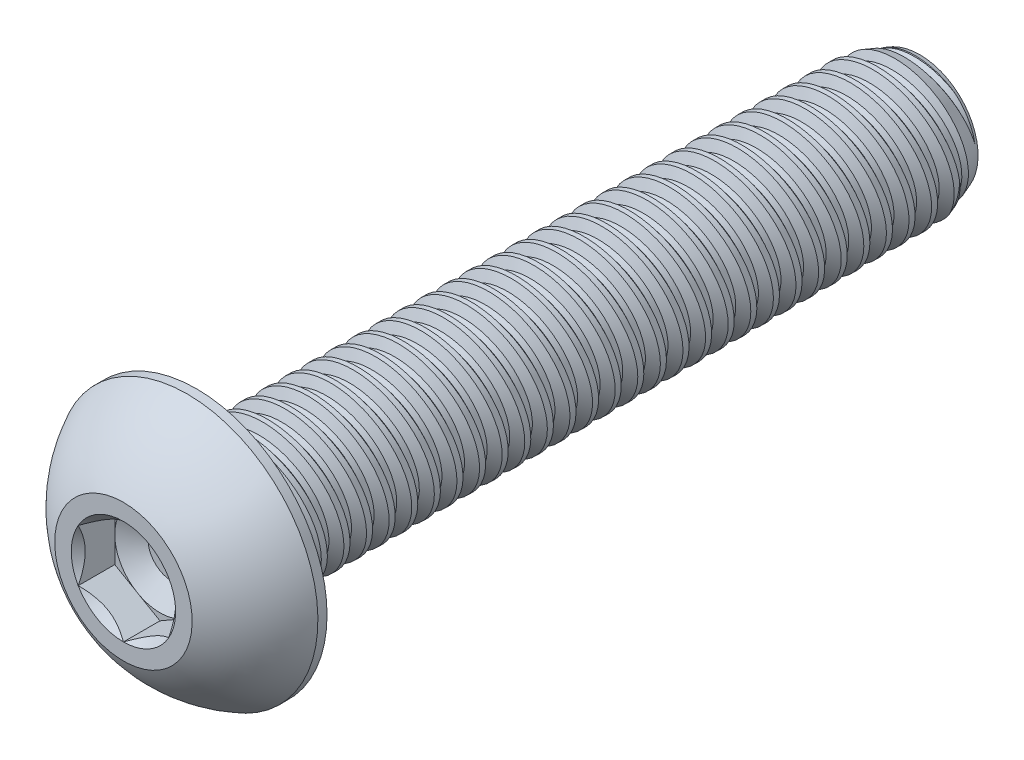
SolidWorks part; units mm, degrees
ref_plane "Front" through (0, 0, 0) normal (0, 0, 1) x (1, 0, 0)
ref_plane "Top" through (0, 0, 0) normal (0, 1, 0) x (1, 0, 0)
ref_plane "Right" through (0, 0, 0) normal (1, 0, 0) x (0, 0, -1)
sketch "Sketch1" plane through (0, 0, 0) normal (1, 0, 0) x (0, 0, -1)
  line L0 (0, 0) -> (-2.5654, 0) construction
  line L1 (0, 0) -> (25.4, 0)
  line L2 (0, 0) -> (0, 2.413)
  line L3 (0, 2.413) -> (25.4, 2.413)
  line L4 (25.4, 0) -> (25.4, 2.413)
  line L5 (0, -2.413) -> (25.4, -2.413) construction
  dimension "D1" = 25.4
  dimension "Thread Dia" = 4.826
  dimension "Length" = 25.4
  dimension "Head Height" = 2.5654
revolve "Revolve1" add sketch "Sketch1" angle 360 about L0
ref_plane "Plane1" through (0, 0, 2.5654) normal (0, 0, 1) x (1, 0, 0)
sketch "Sketch2" plane through (0, 0, 0) normal (1, 0, 0) x (0, 0, -1)
  line L0 (0, 2.413) -> (0, -2.413) construction
  line L1 (0, -2.413) -> (0.7938, -2.413) construction
  line L2 (0.7938, -2.413) -> (0, 2.413) construction
  line L3 (0, 2.413) -> (0.0979, 2.4291) construction
  line L4 (0.0979, 2.4291) -> (0.7832, 2.5418)
  line L5 (0.7832, 2.5418) -> (0.6082, 2.0776)
  line L6 (0.6082, 2.0776) -> (0.4124, 2.0454)
  line L7 (0.4124, 2.0454) -> (0.0979, 2.4291)
  line L8 (0.5103, 2.0615) -> (0.4406, 2.4855) construction
  line L9 (0, -2.413) -> (25.4, -2.413) construction
  line L10 (0, 2.413) -> (25.4, 2.413) construction
  line L12 (0.4525, 2.413) -> (1.2462, -2.413) construction
  line L13 (0, -0.1397) -> (1.6987, 0.1397) construction
  line L15 (0, 0) -> (0, 2.413) construction
  point P19 (0.8494, 0)
  dimension "D1" = 60
  dimension "Thread Pitch" = 0.7937
  dimension "D2" = 0.0992
  dimension "D3" = 0.1984
  dimension "D4" = 0.7937
revolve "Cut-Revolve1" cut sketch "Sketch2" angle 360 about L13
sketch "Sketch3" plane through (0, 0, 0) normal (1, 0, 0) x (0, 0, -1)
  line L0 (25.4, 2.0454) -> (24.3901, 2.413)
  line L1 (24.3901, 2.413) -> (25.4, 2.413)
  line L2 (25.4, 2.413) -> (25.4, 2.0454)
  line L3 (0, 2.413) -> (25.4, 2.413) construction
  line L4 (25.4, 0) -> (25.4, 2.413) construction
  line L5 (24.3901, 0) -> (0, 0) construction
  line L6 (24.3901, 2.413) -> (24.3901, -2.413) construction
  line L7 (0, -2.413) -> (25.4, -2.413) construction
  dimension "D1" = 20
  dimension "D2" = 4.826
revolve "Cut-Revolve2" cut sketch "Sketch3" angle 360 about L5
pattern_linear "LPattern1" count 32 spacing 0.7937 along (0, 0, -1) of "Cut-Revolve1"
pattern_linear "LPattern2" count 2 spacing 0.7937 along (0, 0, 1) of "Cut-Revolve1"
sketch "Sketch4" plane through (0, 0, 0) normal (0, 0, 1) x (1, 0, 0)
  circle A0 centre (0, 0) radius 4.5847
  dimension "Head Dia" = 9.1694
extrude "Extrude1" add sketch "Sketch4" along normal up to surface (2.5654 mm away) up to plane "Plane1"
sketch "Sketch9" plane through (0, 0, 0) normal (1, 0, 0) x (0, 0, -1)
  line L0 (0, 4.5847) -> (-0.3207, 4.5847)
  line L1 (0, 4.5847) -> (0, 4.9054)
  line L2 (0, 4.9054) -> (-2.8861, 4.9054)
  line L3 (0, 0) -> (-2.5654, 0) construction
  line L4 (-2.8861, 4.9054) -> (-2.8861, 2.413)
  line L5 (-2.8861, 2.413) -> (-2.5654, 2.413)
  line L6 (0, 0) -> (0, 2.413) construction
  line L10 (0, 4.5847) -> (-2.5654, 4.5847) construction
  line L11 (0, 2.413) -> (25.4, 2.413) construction
  line L12 (-2.5654, 4.5847) -> (-2.5654, -4.5847) construction
  arc A0 (-2.5654, 2.413) -> (-0.3207, 4.5847) centre (1.942, 0) cw
  dimension "Side Head Height" = 0.3207
revolve "Cut-Revolve3" cut sketch "Sketch9" angle 360 about L3
sketch "Sketch6" plane through (0, 0, 2.5654) normal (0, 0, 1) x (1, 0, 0)
  line L1 (0, -1.8331) -> (1.5875, -0.9165)
  line L2 (1.5875, -0.9165) -> (1.5875, 0.9165)
  line L3 (1.5875, 0.9165) -> (0, 1.8331)
  line L4 (0, 1.8331) -> (-1.5875, 0.9165)
  line L5 (-1.5875, 0.9165) -> (-1.5875, -0.9165)
  line L6 (-1.5875, -0.9165) -> (0, -1.8331)
  circle A0 centre (0, 0) radius 1.5875 construction
  dimension "Hex" = 3.175
extrude "Cut-Extrude1" cut sketch "Sketch6" against normal blind 1.2827
sketch "Sketch7" plane through (0, 0, 2.5654) normal (0, 0, 1) x (1, 0, 0)
  circle A0 centre (0, 0) radius 1.8331
extrude "Cut-Extrude4" cut sketch "Sketch7" against normal blind 1.2827 draft 45
sketch "Sketch8" plane through (0, 0, 1.2827) normal (0, 0, 1) x (1, 0, 0)
  circle A0 centre (0, 0) radius 1.5875 construction
  circle A1 centre (0, 0) radius 1.5875
extrude "Cut-Extrude5" cut sketch "Sketch8" against normal blind 0.4276 draft 60
equation "\"D2@Sketch2\"=\"Thread Pitch@Sketch2\"/8"
equation "\"D3@Sketch2\"=\"Thread Pitch@Sketch2\"/4"
equation "\"D4@Sketch2\"=\"Thread Pitch@Sketch2\""
equation "\"D3@LPattern1\"=\"Thread Pitch@Sketch2\""
equation "\"D1@Cut-Extrude1\"=\"Head Height@Sketch1\"/2"
equation "\"D1@Cut-Extrude4\"=\"D1@Cut-Extrude1\""
equation "\"D1@Cut-Extrude5\"=\"D1@Cut-Extrude1\"/3"
equation "\"D1@LPattern1\"=\"D1@Sketch1\"/\"Thread Pitch@Sketch2\""
equation "\"D3@LPattern2\"=\"Thread Pitch@Sketch2\""
equation "\"Side Head Height@Sketch9\"=\"Head Height@Sketch1\"/8"
